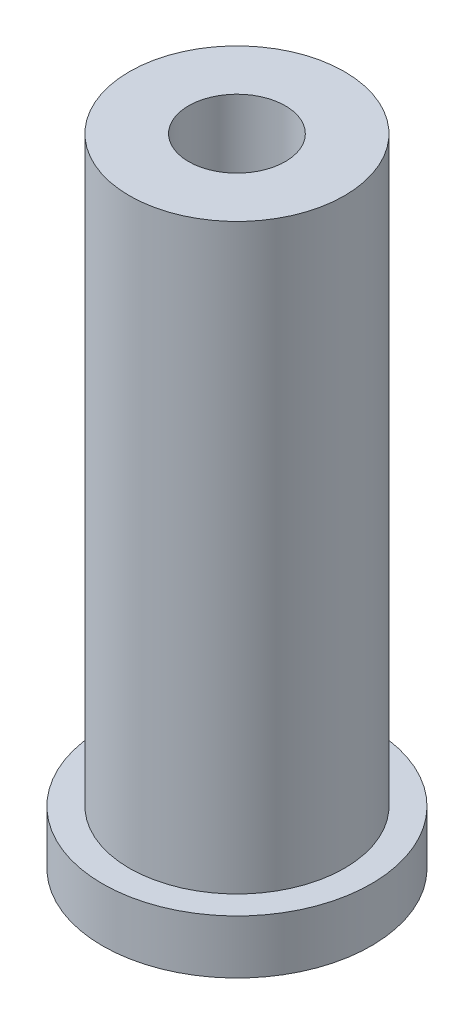
SolidWorks part; units mm, degrees
ref_plane "前基準面" through (0, 0, 0) normal (0, 0, 1) x (1, 0, 0)
ref_plane "上基準面" through (0, 0, 0) normal (0, 1, 0) x (1, 0, 0)
ref_plane "右基準面" through (0, 0, 0) normal (1, 0, 0) x (0, 0, -1)
ref_axis "基準軸1" through (0, -55, 0) along (0, 1, 0)
ref_axis "基準軸2" through (-88.99, 0, 0) along (1, 0, 0)
ref_axis "基準軸3" through (0, 0, 55) along (0, 0, -1)
sketch "草圖1" plane through (0, 0, 0) normal (0, 1, 0) x (1, 0, 0)
  circle A0 centre (0, 0) radius 2.7
  circle A1 centre (0, 0) radius 7.5
  dimension "D1" = 5.4
  dimension "D2" = 15
extrude "填料-伸長1" add sketch "草圖1" along normal blind 3
sketch "草圖3" plane through (0, 3, 0) normal (0, 1, 0) x (1, 0, 0)
  circle A0 centre (0, 0) radius 2.7
  circle A1 centre (0, 0) radius 4
  dimension "D1" = 5.4
  dimension "D2" = 8
extrude "填料-伸長3" add sketch "草圖3" along normal blind 32.5
sketch "草圖4" plane through (0, 35.5, 0) normal (0, 1, 0) x (1, 0, 0)
  circle A0 centre (0, 0) radius 2.7
  circle A1 centre (0, 0) radius 6
  dimension "D1" = 12
  dimension "D2" = 5.4
extrude "填料-伸長4" add sketch "草圖4" against normal up to surface (32.5 mm away) up to face at (0, 3, 7.5)
